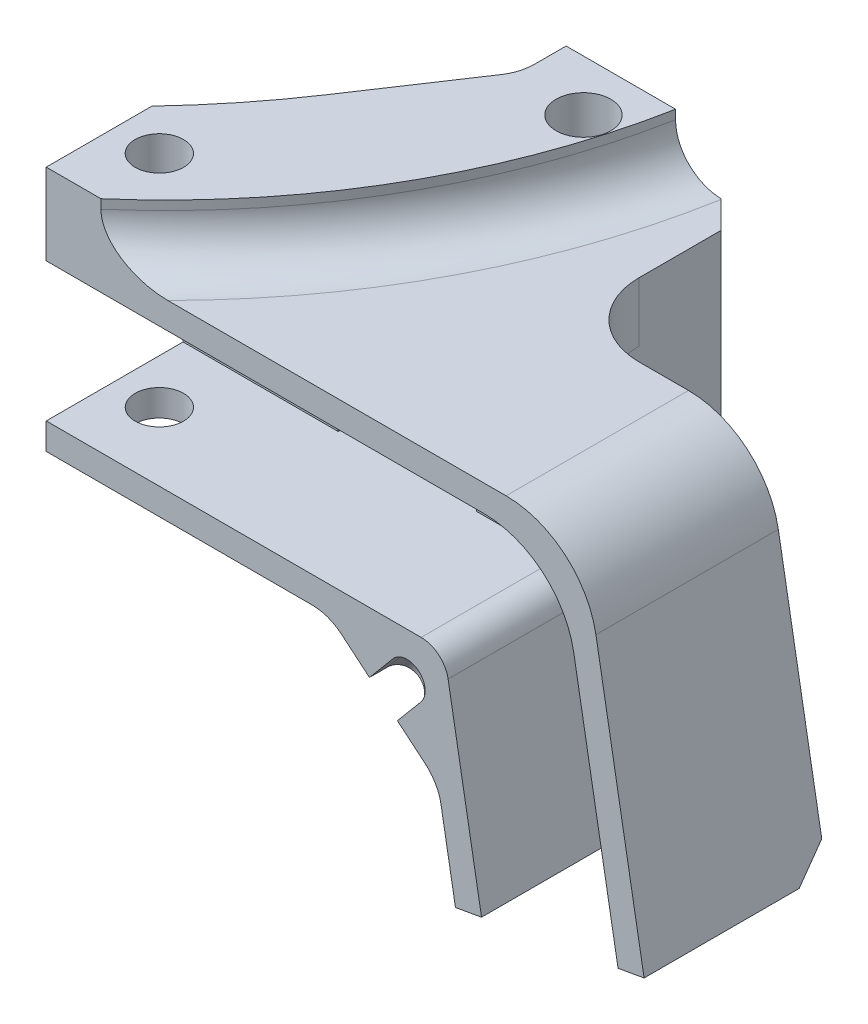
SolidWorks part; units mm, degrees
material "PLA"
ref_plane "前视基准面" through (0, 0, 0) normal (0, 0, 1) x (1, 0, 0)
ref_plane "上视基准面" through (0, 0, 0) normal (0, 1, 0) x (1, 0, 0)
ref_plane "右视基准面" through (0, 0, 0) normal (1, 0, 0) x (0, 0, -1)
sketch "草图1" plane through (0, 0, 0) normal (0, 0, 1) x (1, 0, 0)
  line L0 (0, 0) -> (-50, 0) construction
  line L1 (0, 0) -> (5.2094, -29.5442) construction
  line L2 (-50, -10.5) -> (-50, 10.5)
  line L3 (-50, 10.5) -> (0.4195, 10.5)
  line L4 (10.2676, 2.2365) -> (15.5499, -27.7209)
  line L5 (15.5499, -27.7209) -> (-5.131, -31.3675)
  line L6 (-5.131, -31.3675) -> (-6.7219, -22.3452)
  line L7 (-8.432, -19.3832) -> (-17.6245, -11.6698)
  line L8 (-20.8385, -10.5) -> (-50, -10.5)
  line L9 (-13.0283, -15.5265) -> (0, 0) construction
  arc A0 (0.4195, 10.5) -> (10.2676, 2.2365) centre (0.4195, 0.5) cw
  arc A1 (-6.7219, -22.3452) -> (-8.432, -19.3832) centre (-11.646, -23.2135) ccw
  arc A2 (-17.6245, -11.6698) -> (-20.8385, -10.5) centre (-20.8385, -15.5) ccw
  circle A3 centre (-10, 0) radius 1.65
  circle A4 centre (-40, 0) radius 1.65
  circle A5 centre (1.7365, -9.8481) radius 1.65
  circle A6 centre (4.3412, -24.6202) radius 1.65
  point P17 (5.2094, -29.5442)
  dimension "D6" = 10
  dimension "D7" = 5
  dimension "D8" = 15
  dimension "D9" = 10
  dimension "D10" = 10
  dimension "D11" = 30
  dimension "D12" = 3.3
  dimension "D1" = 100
  dimension "D2" = 50
  dimension "D3" = 30
  dimension "D4" = 12
  dimension "D5" = 21
extrude "凸台-拉伸1" add sketch "草图1" against normal blind 20
sketch "草图2" plane through (0, 0, 0) normal (0, 0, 1) x (1, 0, 0)
  line L0 (0, 0) -> (5.2094, -29.5442) construction
  line L1 (-5.131, -31.3675) -> (15.5499, -27.7209) construction
  line L2 (0, 0) -> (-50, 0) construction
  line L3 (-50, 10.5) -> (-50, -10.5) construction
  line L4 (-50, 7.6) -> (-2.0138, 7.6)
  line L5 (7.8342, -0.6635) -> (12.694, -28.2245)
  line L6 (-2.2751, -30.864) -> (-5.94, -10.0791)
  line L7 (-8.8945, -7.6) -> (-50, -7.6)
  line L8 (-2.2751, -30.864) -> (12.694, -28.2245)
  line L9 (-50, 7.6) -> (-50, -7.6)
  arc A0 (-2.0138, 7.6) -> (7.8342, -0.6635) centre (-2.0138, -2.4) cw
  arc A1 (-5.94, -10.0791) -> (-8.8945, -7.6) centre (-8.8945, -10.6) ccw
  dimension "D2" = 10
  dimension "D3" = 3
  dimension "D1" = 15.2
extrude "切除-拉伸1" cut sketch "草图2" against normal blind 15
sketch "草图3" plane through (0, 0, -20) normal (0, 0, -1) x (-1, 0, 0)
  line L0 (-0.4195, 10.5) -> (50, 10.5) construction
  line L1 (33, 10.5) -> (13, 10.5)
  line L2 (33, 10.5) -> (33, -10.5)
  line L3 (33, -10.5) -> (13, -10.5)
  line L4 (13, 10.5) -> (13, -10.5)
  line L5 (50, -10.5) -> (20.8385, -10.5) construction
  line L6 (18, 10.5) -> (18, -10.5) construction
  line L7 (50, 10.5) -> (50, -10.5) construction
  dimension "D1" = 32
  dimension "D2" = 15
  dimension "D3" = 5
extrude "凸台-拉伸2" add sketch "草图3" along normal blind 20
sketch "草图4" plane through (0, 0, -40) normal (0, 0, -1) x (-1, 0, 0)
  line L0 (33, -10.5) -> (33, 10.5) construction
  line L1 (33, 7.6) -> (17.8, 7.6)
  line L2 (33, 7.6) -> (33, -7.6)
  line L3 (33, -7.6) -> (17.8, -7.6)
  line L4 (17.8, 7.6) -> (17.8, -7.6)
  point P6 (33, 0)
  dimension "D1" = 15.2
extrude "切除-拉伸2" cut sketch "草图4" against normal through all
sketch "草图5" plane through (0, 10.5, 0) normal (0, 1, 0) x (1, 0, 0)
  line L0 (-33, 40) -> (-33, 20) construction
  line L1 (0.4195, 0) -> (-50, 0) construction
  circle A0 centre (-25.5, 34.4) radius 1.65
  dimension "D1" = 7.5
  dimension "D2" = 3.3
  dimension "D3" = 34.4
extrude "切除-拉伸3" cut sketch "草图5" against normal through all
sketch "草图6" plane through (-13, 0, 0) normal (1, 0, 0) x (0, 0, -1)
  line L0 (20, 10.5) -> (20, -10.5) construction
  circle A0 centre (27.4, 0) radius 1.65
  dimension "D1" = 7.4
  dimension "D2" = 3.3
extrude "切除-拉伸4" cut sketch "草图6" against normal up to next
fillet "圆角1" radius 8 2 edges at (-16.9192, -10.5, -20) (-13, 0, -20)
sketch "草图7" plane through (0, 0, -20) normal (0, 0, -1) x (-1, 0, 0)
  line L0 (13, 10.5) -> (13, -10.5) construction
  line L1 (13, 4) -> (5, 4)
  line L2 (13, 4) -> (13, -4)
  line L3 (13, -4) -> (5, -4)
  line L4 (5, 4) -> (5, -4)
  line L5 (5, -18.5) -> (5, 10.5) construction
  point P8 (5, 0)
  dimension "D1" = 8
extrude "切除-拉伸5" cut sketch "草图7" along normal through all
chamfer "倒角1" distance 10 distance2 15 1 edges at (-33, 9.05, -20) first distance on face at (-38.6667, 0, -20)
fillet "圆角2" radius 5 2 edges at (-33, 9.05, -35) (-43, 9.05, -20)
chamfer "倒角2" distance 3 angle 45 3 edges at (5.2094, -29.5442, -20) (-13, 0, -40) (-50, 0, -20)
sketch "草图8" plane through (0, 0, 0) normal (0, 0, 1) x (1, 0, 0)
  line L0 (-14.5604, -14.2409) -> (-11.9892, -11.1768)
  line L1 (-17.6245, -11.6698) -> (-8.432, -19.3832) construction
  line L2 (-8.925, -13.7479) -> (-11.4962, -16.8121)
  line L3 (-11.4962, -16.8121) -> (-14.5604, -14.2409)
  line L4 (-10.4571, -12.4623) -> (0, 0) construction
  arc A0 (-11.9892, -11.1768) -> (-8.925, -13.7479) centre (-10.4571, -12.4623) cw
  dimension "D1" = 2
  dimension "D2" = 4
extrude "切除-拉伸6" cut sketch "草图8" against normal blind 4
fillet "圆角3" radius 2 3 edges at (-10.2106, -15.28, -4) (-9.1716, -10.9302, -4) (-13.2748, -12.7088, -4)
sketch "草图10" plane through (0, 10.5, 0) normal (0, 1, 0) x (1, 0, 0)
  line L0 (-50, 17) -> (-50, 0) construction
  line L1 (0.4195, 0) -> (-50, 0) construction
  circle A0 centre (-45.1, 7.5) radius 2.65
  dimension "D1" = 4.9
  dimension "D2" = 7.5
  dimension "D3" = 5.3
extrude "切除-拉伸7" cut sketch "草图10" against normal through all
sketch "草图9" plane through (0, 10.5, 0) normal (0, 1, 0) x (1, 0, 0)
  line L3 (-33, 40) -> (-16, 40) construction
  line L6 (-33.8397, 33.7404) -> (-41.5157, 22.2265) construction
  line L7 (-33, 40) -> (-33, 36.5139) construction
  line L8 (0.4195, 0) -> (-50, 0) construction
  line L11 (-33.8397, 33.7404) -> (-41.5157, 22.2265)
  line L12 (-33, 40) -> (-33, 36.5139)
  line L13 (-33, 40) -> (-21, 40)
  line L14 (-50, 17) -> (-50, 0) construction
  line L15 (-44, 0) -> (-50, 0)
  line L16 (-50, 11.5866) -> (-50, 0)
  arc A0 (-44, 0) -> (-21, 40) centre (-89.7929, 52.9434) ccw
  arc A2 (-33.8397, 33.7404) -> (-33, 36.5139) centre (-38, 36.5139) ccw construction
  arc A4 (-33.8397, 33.7404) -> (-33, 36.5139) centre (-38, 36.5139) ccw
  circle A5 centre (-45.1, 7.5) radius 2.65 construction
  circle A7 centre (-45.1, 7.5) radius 2.65
  circle A8 centre (-25.5, 34.4) radius 3
  arc A9 (-41.5157, 22.2265) -> (-50, 11.5866) centre (-108.0797, 66.6025) cw
  dimension "D1" = 70
  dimension "D4" = 6
  dimension "D5" = 80
  dimension "D2" = 12
  dimension "D3" = 6
extrude "凸台-拉伸3" add sketch "草图9" along normal blind 6
fillet "圆角4" radius 5 1 edges at (-29.1095, 10.5, -18.0505)
fillet "圆角5" radius 3 1 edges at (-45.5312, 10.5, -16.7258)
